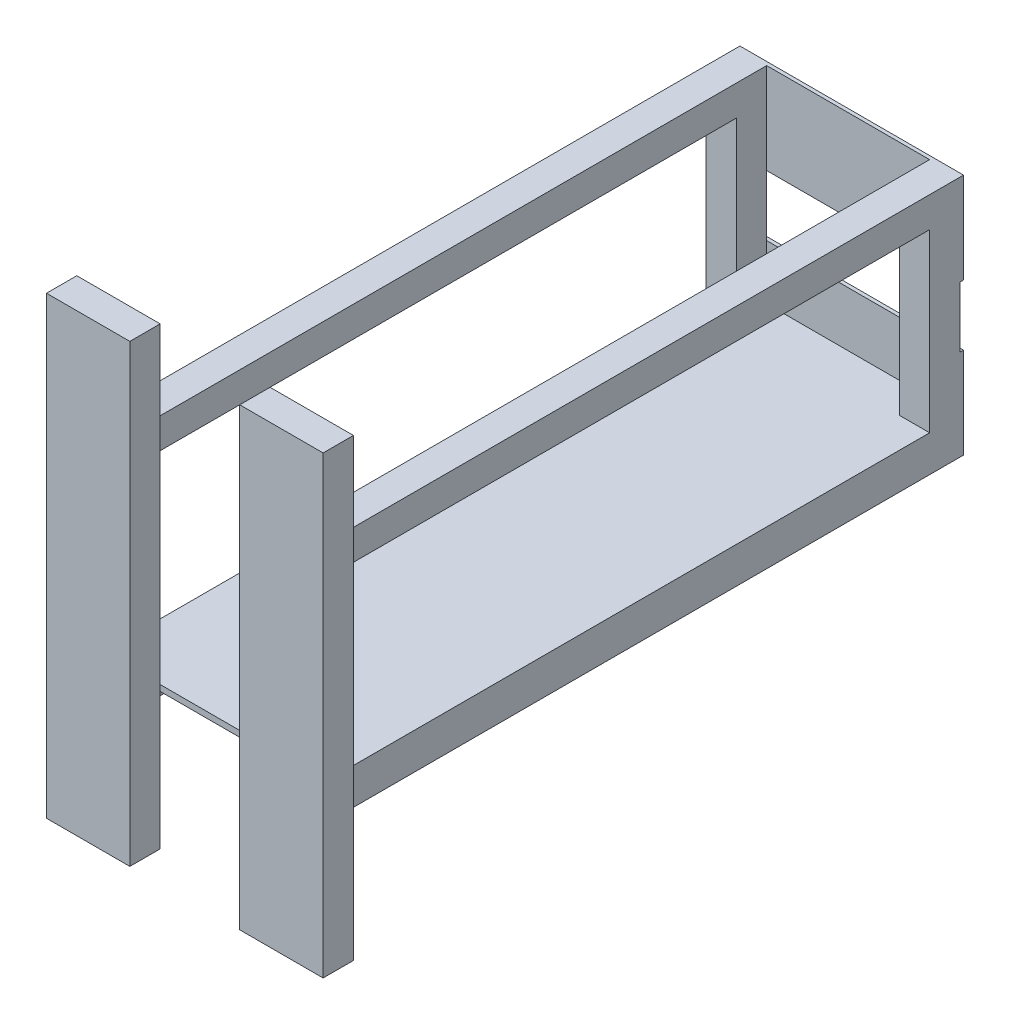
SolidWorks part; units mm, degrees
material "Pine"
ref_plane "Front Plane" through (0, 0, 0) normal (0, 0, 1) x (1, 0, 0)
ref_plane "Top Plane" through (0, 0, 0) normal (0, 1, 0) x (1, 0, 0)
ref_plane "Right Plane" through (0, 0, 0) normal (1, 0, 0) x (0, 0, -1)
sketch "Sketch1" plane through (0, 0, 0) normal (0, 0, 1) x (1, 0, 0)
  line L1 (0, 0) -> (374.65, 0)
  line L2 (0, 0) -> (0, 406.4)
  line L3 (0, 406.4) -> (374.65, 406.4)
  line L4 (374.65, 0) -> (374.65, 406.4)
  line L5 (0, 406.4) -> (50.8, 406.4)
  line L6 (0, 406.4) -> (0, 355.6)
  line L7 (0, 355.6) -> (50.8, 355.6)
  line L8 (50.8, 406.4) -> (50.8, 355.6)
  line L9 (0, 0) -> (50.8, 0)
  line L10 (0, 0) -> (0, 50.8)
  line L11 (0, 50.8) -> (50.8, 50.8)
  line L12 (50.8, 0) -> (50.8, 50.8)
  line L13 (374.65, 0) -> (323.85, 0)
  line L14 (374.65, 0) -> (374.65, 50.8)
  line L15 (374.65, 50.8) -> (323.85, 50.8)
  line L16 (323.85, 0) -> (323.85, 50.8)
  line L17 (374.65, 406.4) -> (323.85, 406.4)
  line L18 (374.65, 406.4) -> (374.65, 355.6)
  line L19 (374.65, 355.6) -> (323.85, 355.6)
  line L20 (323.85, 406.4) -> (323.85, 355.6)
  dimension "D1" = 406.4
  dimension "D2" = 374.65
  dimension "D3" = 50.8
  dimension "D4" = 50.8
  dimension "D5" = 50.8
  dimension "D6" = 50.8
  dimension "D7" = 50.8
  dimension "D8" = 50.8
  dimension "D9" = 50.8
  dimension "D10" = 50.8
extrude "Boss-Extrude1" add sketch "Sketch1" along normal blind 6 contours L3 L4 L1 L2
extrude "Boss-Extrude2" add sketch "Sketch1<5>" along normal blind 1066.8 contours L9 L12 L11 L10 | L14 L15 L16 L13 | L17 L20 L19 L18 | L6 L7 L8 L5
sketch "Sketch1<5>" plane through (0, 0, 0) normal (0, 0, 1) x (1, 0, 0) same geometry as "Sketch1"
sketch "Sketch3" plane through (0, 0, 1066.8) normal (0, 0, 1) x (1, 0, 0)
  line L9 (349.25, 0) -> (349.25, 406.4) construction
  line L11 (25.4, 406.4) -> (25.4, 0) construction
  line L13 (0, 406.4) -> (50.8, 406.4) construction
  line L14 (374.65, 355.6) -> (323.85, 355.6) construction
  line L15 (0, 0) -> (50.8, 0) construction
  line L16 (0, 355.6) -> (0, 406.4) construction
  line L17 (374.65, 0) -> (323.85, 0) construction
  line L21 (374.65, 406.4) -> (323.85, 406.4) construction
  line L23 (-44.45, -177.8) -> (95.25, -177.8)
  line L24 (-44.45, -177.8) -> (-44.45, 584.2)
  line L25 (-44.45, 584.2) -> (95.25, 584.2)
  line L26 (95.25, -177.8) -> (95.25, 584.2)
  line L27 (-44.45, -177.8) -> (95.25, 584.2) construction
  line L28 (-44.45, 584.2) -> (95.25, -177.8) construction
  line L29 (279.4, -177.8) -> (419.1, -177.8)
  line L30 (279.4, -177.8) -> (279.4, 584.2)
  line L31 (279.4, 584.2) -> (419.1, 584.2)
  line L32 (419.1, -177.8) -> (419.1, 584.2)
  line L33 (279.4, -177.8) -> (419.1, 584.2) construction
  line L34 (279.4, 584.2) -> (419.1, -177.8) construction
  point P15 (349.25, 0)
  point P16 (25.4, 203.2)
  point P28 (349.25, 203.2)
  dimension "D1" = 139.7
  dimension "D2" = 762
  dimension "D3" = 762
  dimension "D4" = 139.7
extrude "Boss-Extrude4" add sketch "Sketch3" along normal blind 50.8 contours L24 L25 L26 L23 | L30 L31 L32 L29
sketch "Sketch4" plane through (0, 50.8, 0) normal (0, 1, 0) x (1, 0, 0)
  line L1 (0, -6) -> (374.65, -6)
  line L2 (0, -6) -> (0, -1066.8)
  line L3 (0, -1066.8) -> (374.65, -1066.8)
  line L4 (374.65, -6) -> (374.65, -1066.8)
extrude "Boss-Extrude5" add sketch "Sketch4" along normal blind 10
sketch "Sketch5" plane through (0, 0, 0) normal (0, 0, -1) x (-1, 0, 0)
  line L0 (-187.325, 0) -> (-187.325, 152.4)
  line L1 (0, 0) -> (-374.65, 0) construction
  line L2 (-187.325, 406.4) -> (-187.325, 254)
  line L3 (0, 406.4) -> (-374.65, 406.4) construction
  line L4 (-187.325, 152.4) -> (-187.325, 254)
  line L5 (0, 0) -> (0, 406.4) construction
  line L6 (-374.65, 152.4) -> (0, 152.4)
  line L7 (-374.65, 152.4) -> (-374.65, 254)
  line L8 (-374.65, 254) -> (0, 254)
  line L9 (0, 152.4) -> (0, 254)
  line L10 (-374.65, 152.4) -> (0, 254) construction
  line L11 (-374.65, 254) -> (0, 152.4) construction
  point P8 (-187.325, 203.2)
  dimension "D1" = 152.4
  dimension "D2" = 152.4
extrude "Cut-Extrude1" cut sketch "Sketch5" against normal blind 10 contours L8 L9 L6 L7
sketch "Sketch6" plane through (0, 355.6, 0) normal (0, -1, 0) x (1, 0, 0)
  line L0 (0, 6) -> (0, 56.8)
  line L1 (0, 1066.8) -> (0, 6) construction
  line L2 (0, 56.8) -> (50.8, 56.8)
  line L3 (50.8, 1066.8) -> (50.8, 6) construction
  line L4 (50.8, 56.8) -> (50.8, 6)
  line L5 (323.85, 6) -> (323.85, 56.8)
  line L6 (323.85, 1066.8) -> (323.85, 6) construction
  line L7 (323.85, 56.8) -> (374.65, 56.8)
  line L8 (374.65, 1066.8) -> (374.65, 6) construction
  line L9 (374.65, 56.8) -> (374.65, 6)
  line L10 (0, 6) -> (50.8, 6)
  line L11 (374.65, 6) -> (323.85, 6)
  dimension "D1" = 50.8
  dimension "D2" = 50.8
  dimension "D3" = 50.8
extrude "Boss-Extrude7" add sketch "Sketch6" along normal up to next
